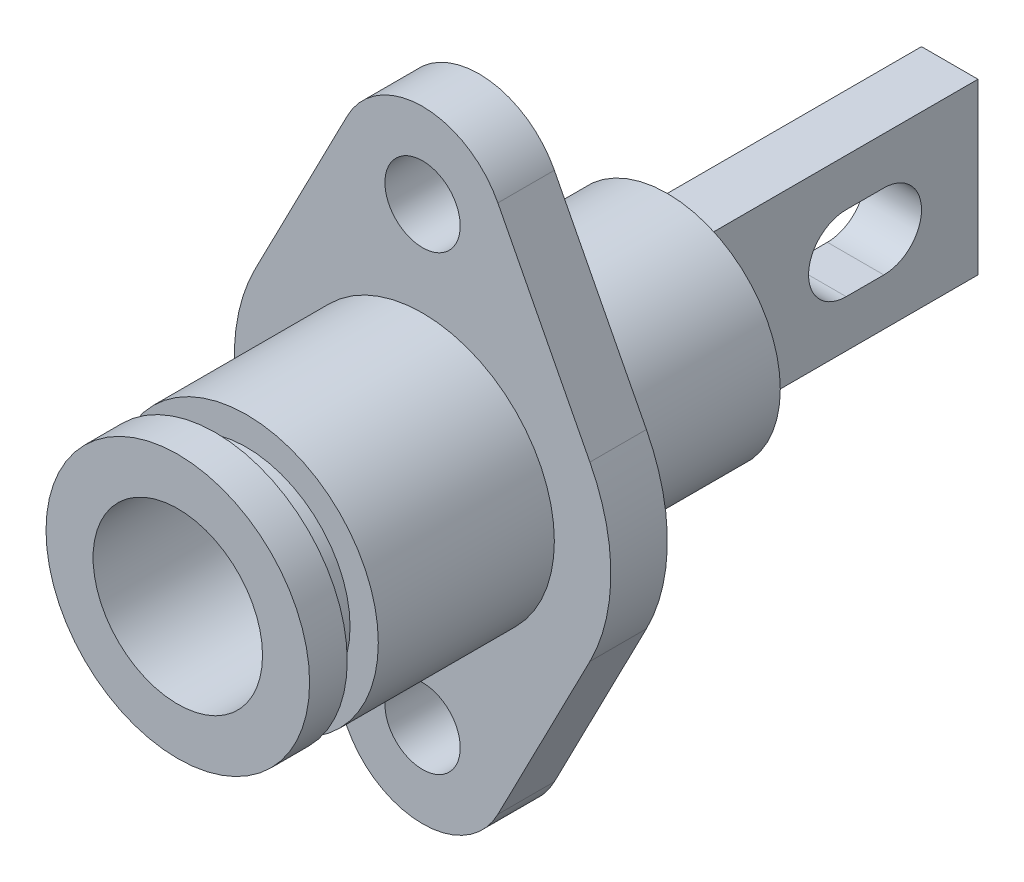
SolidWorks part; units mm, degrees
material "Custom Plastic"
ref_plane "X-Y Datum" through (0, 0, 0) normal (0, 0, 1) x (1, 0, 0)
ref_plane "X-Z Datum" through (0, 0, 0) normal (0, 1, 0) x (1, 0, 0)
ref_plane "Y-Z Datum" through (0, 0, 0) normal (1, 0, 0) x (0, 0, -1)
sketch "Sketch1" plane through (0, 0, 0) normal (0, 0, 1) x (1, 0, 0)
  line L0 (0, 17) -> (0, -17) construction
  line L1 (-10, 0) -> (10, 0) construction
  line L2 (-3.7696, 14.5084) -> (-8.8878, 4.5833)
  line L3 (3.7696, 14.5084) -> (8.8878, 4.5833)
  line L4 (3.7696, -14.5084) -> (8.8878, -4.5833)
  line L5 (-3.7696, -14.5084) -> (-8.8878, -4.5833)
  line L6 (0, 12) -> (0, -12) construction
  circle A0 centre (0, 0) radius 10
  circle A5 centre (0, 12) radius 2
  circle A6 centre (0, -12) radius 2
  circle A7 centre (0, 12) radius 4.5
  circle A8 centre (0, -12) radius 4.5
  point P4 (0, 0)
  point P8 (0, 0)
  point P26 (0, 0)
  dimension "D3" = 4
  dimension "D5" = 24
  dimension "D1" = 34
  dimension "D2" = 20
  dimension "D4" = 24
  dimension "D6" = 2.5
extrude "Boss-Extrude1" add sketch "Sketch1" along normal blind 3 contours A7 A0 A5 | A7 L2 A0 | A7 A0 L3 | A0 A8 A7 | A0 A7 | L5 A8 A0 | A8 A0 | A8 A0 A6 | A0 A8 L4 region at (-5.5325, 9.5178, 0) region at (0, 16.3849, 0) region at (0, 0, 0) region at (5.5325, 9.5178, 0) region at (0, 8.8462, 0) region at (-5.5325, -9.5178, 0) region at (-4.3707, -11.6473, 0) region at (0, -8.8462, 0) region at (5.5325, -9.5178, 0)
sketch "Sketch2" plane through (0, 0, 3) normal (0, 0, 1) x (1, 0, 0)
  circle A0 centre (0, 0) radius 7
  dimension "D1" = 14
extrude "Boss-Extrude2" add sketch "Sketch2" along normal blind 9.35
sketch "Sketch3" plane through (0, 0, 0) normal (0, 0, -1) x (-1, 0, 0)
  circle A0 centre (0, 0) radius 7.5
  dimension "D1" = 15
extrude "Boss-Extrude3" add sketch "Sketch3" along normal blind 0.5
sketch "Sketch4" plane through (0, 0, -0.5) normal (0, 0, -1) x (-1, 0, 0)
  line L1 (-1.5, 4.5) -> (1.5, 4.5)
  line L2 (-1.5, 4.5) -> (-1.5, -4.5)
  line L3 (-1.5, -4.5) -> (1.5, -4.5)
  line L4 (1.5, 4.5) -> (1.5, -4.5)
  line L5 (-1.5, 4.5) -> (1.5, -4.5) construction
  line L6 (-1.5, -4.5) -> (1.5, 4.5) construction
  point P0 (0, 0)
  dimension "D1" = 9
  dimension "D2" = 3
extrude "Boss-Extrude4" add sketch "Sketch4" along normal blind 24.5
sketch "Sketch5" plane through (0, 0, -0.5) normal (0, 0, -1) x (-1, 0, 0)
  circle A0 centre (0, 0) radius 6
  dimension "D1" = 12
extrude "Boss-Extrude5" add sketch "Sketch5" along normal blind 9.5
sketch "Sketch8" plane through (0, 0, 12.35) normal (0, 0, 1) x (1, 0, 0)
  circle A0 centre (0, 0) radius 5.5
extrude "Boss-Extrude6" add sketch "Sketch8" along normal blind 1.65
sketch "Sketch9" plane through (0, 0, 14) normal (0, 0, 1) x (1, 0, 0)
  circle A0 centre (0, 0) radius 7
extrude "Boss-Extrude7" add sketch "Sketch9" along normal blind 2
sketch "Sketch10" plane through (0, 0, 16) normal (0, 0, 1) x (1, 0, 0)
  circle A0 centre (0, 0) radius 4.5
extrude "Cut-Extrude1" cut sketch "Sketch10" against normal blind 25 contours A0
sketch "Sketch14" plane through (1.5, 0, 0) normal (1, 0, 0) x (0, 0, -1)
  line L0 (10, 0) -> (16, 0)
  line L1 (10, 4.5) -> (10, -4.5) construction
  line L2 (16, 0) -> (22, 0)
  line L3 (22, 0) -> (25, 0)
  line L4 (25, 4.5) -> (25, -4.5) construction
sketch "Sketch15" plane through (1.5, 0, 0) normal (1, 0, 0) x (0, 0, -1)
  line L0 (22, 0) -> (20, 0)
  line L1 (16, 0) -> (22, 0) construction
  line L2 (16, 0) -> (18, 0)
  line L3 (20, 0) -> (18, 0) construction
  line L4 (20, -2) -> (18, -2)
  line L5 (20, 2) -> (18, 2)
  arc A0 (20, -2) -> (20, 2) centre (20, 0) ccw
  arc A1 (18, 2) -> (18, -2) centre (18, 0) ccw
  point P8 (19, 0)
extrude "Cut-Extrude2" cut sketch "Sketch15" against normal blind 3 contours A0 L5 A1 L4
